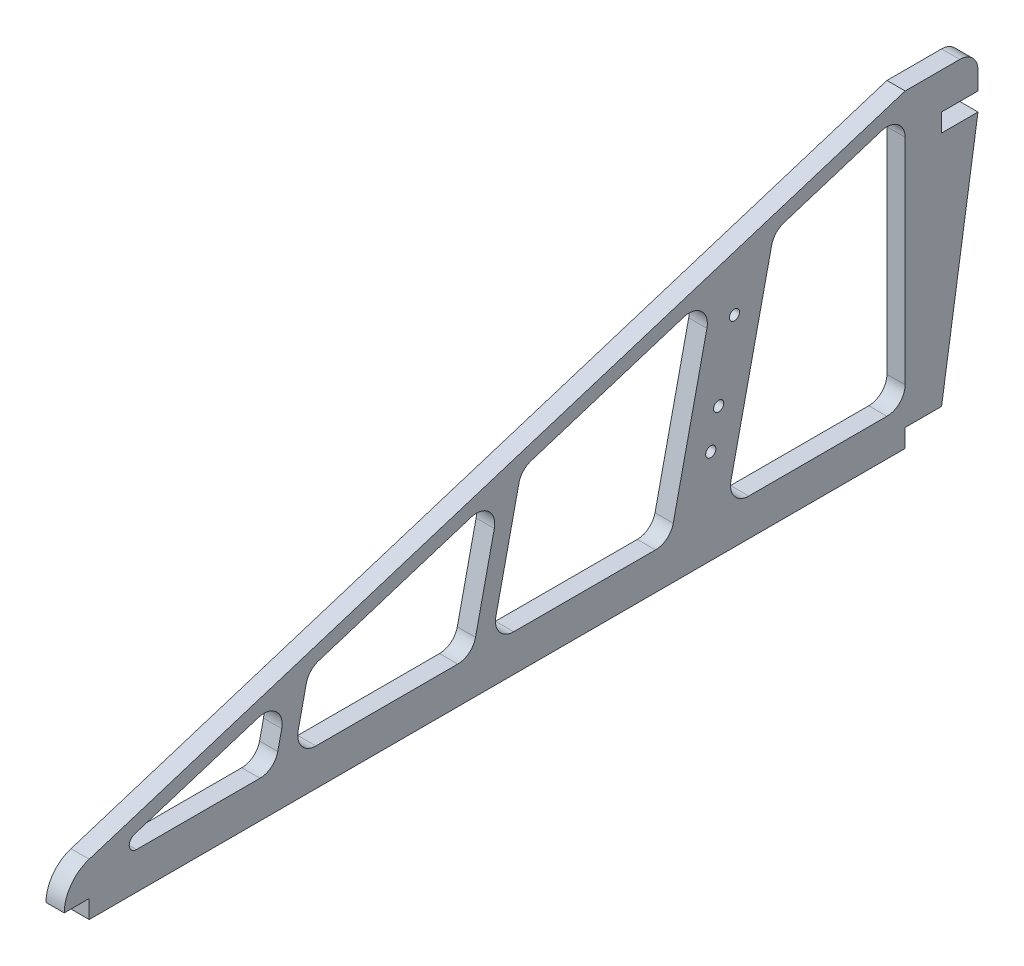
SolidWorks part; units mm, degrees
ref_plane "Front Plane" through (0, 0, 0) normal (0, 0, 1) x (1, 0, 0)
ref_plane "Top Plane" through (0, 0, 0) normal (0, 1, 0) x (1, 0, 0)
ref_plane "Right Plane" through (0, 0, 0) normal (1, 0, 0) x (0, 0, -1)
sketch "Sketch1" plane through (0, 0, 0) normal (1, 0, 0) x (0, 0, -1)
  line L0 (0, 0) -> (142.24, 0)
  line L1 (142.24, 0) -> (142.24, 3.175)
  line L2 (142.24, 3.175) -> (148.59, 3.175)
  line L3 (0, 0) -> (0, 3.175)
  line L4 (0, 3.175) -> (-4.3539, 3.175)
  line L5 (0, 9.1135) -> (142.24, 53.975)
  line L6 (148.59, 3.175) -> (154.94, 44.45)
  line L7 (142.24, 53.975) -> (154.94, 53.975)
  line L8 (154.94, 53.975) -> (154.94, 47.625)
  line L9 (154.94, 47.625) -> (148.59, 47.625)
  line L10 (148.59, 47.625) -> (148.59, 44.45)
  line L11 (148.59, 44.45) -> (154.94, 44.45)
  arc A0 (-4.3539, 3.175) -> (0, 9.1135) centre (1.873, 3.175) cw
  point P3 (148.59, 53.975)
  point P21 (154.94, 50.8)
  dimension "D1" = 142.24
  dimension "D2" = 3.175
  dimension "D3" = 6.35
  dimension "D4" = 3.175
  dimension "D5" = 6.35
  dimension "D6" = 6.35
  dimension "D7" = 50.8
  dimension "D8" = 4.3539
  dimension "D9" = 6.35
extrude "Boss-Extrude1" add sketch "Sketch1" along normal blind 3.175
sketch "Sketch2" plane through (3.175, 0, 0) normal (1, 0, 0) x (0, 0, -1)
  line L0 (142.24, 3.175) -> (-0.0342, 3.175) construction
  line L1 (0, 6.4501) -> (142.24, 6.4501) construction
  line L2 (142.24, 0) -> (142.24, 3.175) construction
  line L3 (142.24, 51.3117) -> (0, 6.4501) construction
  line L4 (142.24, 53.975) -> (0, 9.1135) construction
  line L10 (142.24, 51.3117) -> (142.24, 6.4501)
  line L11 (142.24, 6.4501) -> (111.0206, 6.4501)
  line L12 (111.0206, 6.4501) -> (119.3632, 44.0965)
  line L13 (119.3632, 44.0965) -> (142.24, 51.3117)
  line L14 (108.874, 40.7882) -> (101.2645, 6.4501)
  line L15 (101.2645, 6.4501) -> (70.045, 6.4501)
  line L16 (70.045, 6.4501) -> (75.3085, 30.2019)
  line L17 (75.3085, 30.2019) -> (108.874, 40.7882)
  line L18 (71.8121, 29.0992) -> (66.793, 6.4501)
  line L19 (66.793, 6.4501) -> (35.5736, 6.4501)
  line L20 (35.5736, 6.4501) -> (38.2467, 18.5129)
  line L21 (38.2467, 18.5129) -> (71.8121, 29.0992)
  line L22 (0, 6.4501) -> (34.7503, 17.4102)
  line L23 (34.7503, 17.4102) -> (32.3215, 6.4501)
  line L24 (32.3215, 6.4501) -> (0, 6.4501)
  point P24 (148.59, 47.625)
  dimension "D3" = 30.48
  dimension "D1" = 2.54
  dimension "D2" = 120
  dimension "D4" = 9.525
  dimension "D6" = 3.175
  dimension "D7" = 3.175
extrude "Cut-Extrude1" cut sketch "Sketch2" against normal through all contours L13 L12 L11 L10 | L17 L16 L15 L14 | L21 L20 L19 L18 | L24 L23 L22 region at (3.175, 25.9698, -129.059) region at (3.175, 21.1334, -89.8569) region at (3.175, 15.3971, -54.7528) region at (3.175, 10.1035, -22.3573)
fillet "Fillet4" radius 3.175 10 edges at (1.5875, 6.4501, -32.3215) (1.5875, 6.4501, -35.5736) (1.5875, 6.4501, -66.793) (1.5875, 6.4501, -70.045) (1.5875, 6.4501, -101.2645) (1.5875, 6.4501, -111.0206) (1.5875, 6.4501, -142.24) (1.5875, 18.5129, -38.2467) (1.5875, 30.2019, -75.3085) (1.5875, 44.0965, -119.3632)
fillet "Fillet5" radius 3.175 4 edges at (1.5875, 17.4102, -34.7503) (1.5875, 29.0992, -71.8121) (1.5875, 40.7882, -108.874) (1.5875, 51.3117, -142.24)
fillet "Fillet6" radius 3.175 1 edges at (1.5875, 53.975, -154.94)
fillet "Fillet7" radius 1.27 1 edges at (1.5875, 6.4501, 0)
sketch "Sketch3" plane through (3.175, 0, 0) normal (1, 0, 0) x (0, 0, -1)
  line L0 (104.7131, 0) -> (114.7531, 45.3058) construction
  line L1 (0, 0) -> (142.24, 0) construction
  line L2 (142.24, 53.975) -> (0, 9.1135) construction
  line L3 (107.6842, 35.4192) -> (101.8158, 8.9382) construction
  line L4 (111.8764, 10.3121) -> (118.9666, 42.3068) construction
  point P2 (112.4808, 35.0521)
  point P3 (109.7331, 22.6529)
  point P12 (87.488, 17.3386)
  point P15 (108.3593, 16.4533)
  dimension "D1" = 12.7
  dimension "D2" = 6.35
hole_wizard "#2-56 Tapped Hole1" positions "3DSketch1" profile "Sketch5" tap size "#2-56" standard "ANSI Inch" end condition through all
sketch3d "3DSketch1"
  line L0 (3.175, 0, -104.7131) -> (3.175, 45.3058, -114.7531) construction
  point P0 (3.175, 35.0521, -112.4808)
  point P3 (3.175, 22.6529, -109.7331)
  point P7 (3.175, 22.6529, -109.7331)
  point P11 (3.175, 22.6529, -109.7331)
  point P13 (3.175, 22.6529, -109.7331)
  point P16 (524.2517, 38.7338, 0)
  point P19 (3.175, 16.4533, -108.3593)
sketch "Sketch5" plane through (3.175, 35.0521, -112.4808) normal (0, 1, 0) x (0, 0, -1)
  line L0 (0, 0) -> (0, 3.175)
  line L1 (0, 3.175) -> (0.889, 3.175)
  line L2 (0.889, 3.175) -> (0.889, 0)
  line L5 (0.889, 0) -> (0, 0)
  line L11 (0, -6.35) -> (0, 107.95) construction
  dimension "Thru Tap Drill Dia." = 1.778
  dimension "Thru Tap Drill Depth" = 3.175
cosmetic thread "Hole Thread1" parameters "D2"=2.1844
cosmetic thread "Hole Thread2" parameters "D2"=2.1844
cosmetic thread "Hole Thread3" parameters "D2"=2.1844
cosmetic thread "Hole Thread4" parameters "D2"=2.1844
cosmetic thread "Hole Thread5" parameters "D2"=2.1844
cosmetic thread "Hole Thread6" parameters "D2"=2.1844
cosmetic thread "Hole Thread7" parameters "D2"=2.1844
